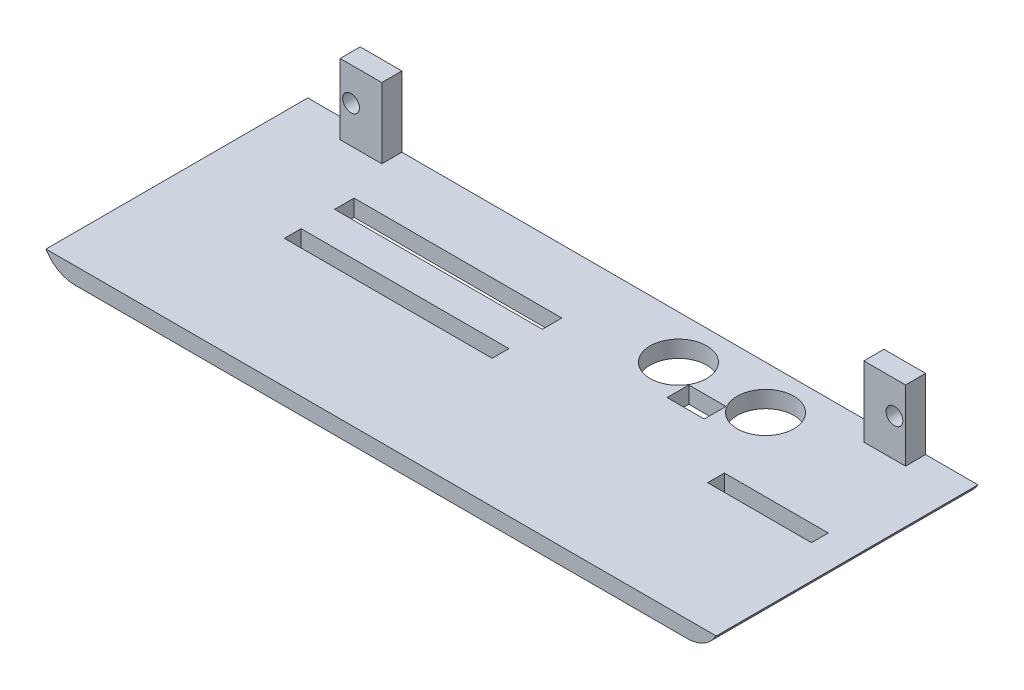
SolidWorks part; units mm, degrees
material "Aleación 1060"
ref_plane "Alzado" through (0, 0, 0) normal (0, 0, 1) x (1, 0, 0)
ref_plane "Planta" through (0, 0, 0) normal (0, 1, 0) x (1, 0, 0)
ref_plane "Vista lateral" through (0, 0, 0) normal (1, 0, 0) x (0, 0, -1)
sketch "Croquis2" plane through (0, 0, 0) normal (0, 0, 1) x (1, 0, 0)
  line L0 (64.1083, -69.3601) -> (64.1083, -63.6754) construction
  line L1 (-99.8917, -75.3601) -> (100.1083, -75.3601)
  line L2 (-99.8917, -75.3601) -> (-99.8917, 74.6399)
  line L3 (-99.8917, 74.6399) -> (100.1083, 74.6399)
  line L4 (100.1083, -75.3601) -> (100.1083, 74.6399)
  line L6 (100.1083, -69.3601) -> (-31.2492, -69.3601) construction
  line L7 (-32.0917, -69.3601) -> (-32.0917, -67.3601) construction
  line L8 (-62.0917, -69.3601) -> (-62.0917, -67.3601) construction
  line L11 (0.1083, -67.3601) -> (0.1083, -75.3601) construction
  line L15 (71.6083, -0.3601) -> (100.1083, -0.3601) construction
  line L34 (-99.8917, -0.3601) -> (-71.3917, -0.3601) construction
  line L35 (-62.0917, 70.6399) -> (64.1083, 70.6399)
  line L38 (-71.3917, -12.9024) -> (-71.3917, 12.1823)
  line L41 (-79.2417, -13.0101) -> (-71.3917, -12.9024)
  line L45 (92.1083, 45.4784) -> (92.1083, -46.1985)
  line L46 (89.1083, 45.8764) -> (89.1083, -46.5966)
  line L47 (84.1083, 12.2899) -> (84.1083, -13.0101)
  line L48 (84.1083, -13.0101) -> (79.4583, -13.0101)
  line L49 (71.6083, -13.0101) -> (71.6083, 12.2899)
  line L52 (79.4583, -13.0101) -> (71.6083, -13.0101)
  line L53 (84.1083, 12.2899) -> (79.4583, 12.2899)
  line L69 (-83.8917, -13.0101) -> (-79.2417, -13.0101)
  line L70 (-83.8917, 12.2899) -> (-83.8917, -13.0101)
  line L71 (-91.8917, 45.4784) -> (-91.8917, -46.1985)
  line L72 (-88.8917, 45.8764) -> (-88.8917, -46.5966)
  line L82 (79.4583, 12.2899) -> (71.6083, 12.2899)
  line L85 (-79.2417, 12.2899) -> (-71.3917, 12.1823)
  line L86 (-83.8917, 12.2899) -> (-79.2417, 12.2899)
  line L99 (-45.6601, 58.1834) -> (-14.3628, 58.1834)
  line L102 (64.1083, 66.6399) -> (-62.0917, 66.6399)
  line L103 (-62.0917, -71.3601) -> (64.1083, -71.3601)
  line L104 (64.1083, -67.3601) -> (-62.0917, -67.3601)
  line L118 (-45.6601, 58.1834) -> (-45.6601, 14.4146)
  line L119 (-45.6601, 14.4146) -> (-14.3628, 14.4146)
  line L120 (-14.3628, 58.1834) -> (-14.3628, 14.4146)
  line L121 (-45.6601, -4.9147) -> (-14.3628, -4.9147)
  line L122 (-45.6601, -4.9147) -> (-45.6601, -48.6834)
  line L123 (-45.6601, -48.6834) -> (-14.3628, -48.6834)
  line L124 (-14.3628, -4.9147) -> (-14.3628, -48.6834)
  line L125 (1.1959, 21.9686) -> (24.7698, 21.9686)
  line L126 (1.1959, 21.9686) -> (1.1959, -23.3553)
  line L127 (1.1959, -23.3553) -> (24.7698, -23.3553)
  line L128 (24.7698, 21.9686) -> (24.7698, -23.3553)
  circle A0 centre (89.1083, -66.5) radius 2
  arc A1 (64.1083, -71.3601) -> (64.1083, -67.3601) centre (64.1083, -69.3601) ccw
  arc A6 (-62.0917, -67.3601) -> (-62.0917, -71.3601) centre (-62.0917, -69.3601) ccw
  circle A8 centre (-88.8917, -66.5) radius 2
  arc A92 (89.1083, -46.5966) -> (92.1083, -46.1985) centre (90.6083, -46.3976) ccw
  arc A97 (-88.8917, -46.5966) -> (-91.8917, -46.1985) centre (-90.3917, -46.3976) cw
  arc A108 (-88.8917, 45.8764) -> (-91.8917, 45.4784) centre (-90.3917, 45.6774) ccw
  arc A109 (89.1083, 45.8764) -> (92.1083, 45.4784) centre (90.6083, 45.6774) cw
  circle A110 centre (89.1083, 65.7798) radius 2
  arc A113 (64.1083, 70.6399) -> (64.1083, 66.6399) centre (64.1083, 68.6399) cw
  arc A146 (-62.0917, 66.6399) -> (-62.0917, 70.6399) centre (-62.0917, 68.6399) cw
  circle A153 centre (-88.8917, 65.7798) radius 2
  circle A154 centre (-80.8654, -59.3601) radius 2.5
  circle A155 centre (81.1083, -59.3601) radius 2.5
  circle A156 centre (81.1083, 58.6399) radius 2.5
  circle A157 centre (-80.8654, 58.6399) radius 2.5
  point P0 (0, 0)
  point P78 (3.0535, -59.0858)
  point P80 (1.1959, -58.7698)
  point P84 (89.4782, -52.7527)
  point P89 (81.5012, -58.7833)
  point P95 (-80.8654, -59.3601)
  point P116 (-91.8917, -0.3601)
  point P120 (-5.0314, -61.027)
  point P121 (11.1384, -58.7698)
  point P128 (84.1083, -0.3601)
  point P135 (71.6083, -0.3601)
  point P139 (-71.3917, -0.3601)
  point P140 (-83.8917, -0.3601)
  point P143 (-88.8917, -0.3601)
  point P144 (0.0463, 58.5996)
  point P149 (89.1083, -0.3601)
  point P150 (92.1083, -0.3601)
  point P155 (81.5012, 58.0631)
  point P171 (49.6083, -0.3601)
  point P173 (46.6083, -0.3601)
  point P228 (1.1959, 58.2649)
  point P247 (7.6372, -0.3601)
  point P258 (-14.3628, -0.3601)
  point P290 (-80.8654, 58.38)
  dimension "D4" = 6
  dimension "D5" = 25
  dimension "D6" = 19.0263
  dimension "D7" = 16
  dimension "D9" = 16
  dimension "D19" = 26.8
  dimension "D32" = 8
  dimension "D22" = 3
  dimension "D8" = 19
  dimension "D1" = 200
  dimension "D2" = 150
  dimension "D10" = 11
  dimension "D11" = 11
  dimension "D35" = 12.65
  dimension "D36" = 5
  dimension "D42" = 4.65
  dimension "D43" = 12.5
extrude "Saliente-Extruir1" add sketch "Croquis2" along normal blind 2
fillet "Redondeo1" radius 10 4 edges at (-99.8917, 74.6399, 1) (-99.8917, -75.3601, 1) (100.1083, -75.3601, 1) (100.1083, 74.6399, 1)
sketch "Sketch1" plane through (0, 0, 2) normal (0, 0, 1) x (1, 0, 0)
  line L0 (-67.0718, 64.6399) -> (-67.0718, 60.6399)
  line L1 (-67.0718, 60.6399) -> (-8.8412, 60.6399)
  line L2 (-8.8412, 60.6399) -> (-8.8412, 3.6399)
  line L3 (-8.8412, 3.6399) -> (-67.0718, 3.6399)
  line L4 (-67.0718, 3.6399) -> (-67.0718, -0.3601)
  line L5 (-67.0718, -0.3601) -> (-8.8412, -0.3601)
  line L6 (-8.8412, -0.3601) -> (-8.8412, -53.3601)
  line L7 (-8.8412, -53.3601) -> (-67.0718, -53.3601)
  line L8 (-67.0718, -53.3601) -> (-67.0718, -57.5747)
  line L9 (-67.0718, -57.5747) -> (-5.0314, -57.5747)
  line L10 (-5.0314, -57.5747) -> (-5.0314, -40.9314)
  line L11 (-5.0314, -40.9314) -> (46.6083, -40.9314)
  line L12 (46.6083, -40.9314) -> (46.6083, -36.9314)
  line L13 (46.6083, -36.9314) -> (-5.0314, -36.9314)
  line L14 (-5.0314, -36.9314) -> (-5.0314, 30.0686)
  line L15 (-5.0314, 30.0686) -> (46.6083, 30.0686)
  line L16 (46.6083, 30.0686) -> (46.6083, 34.0686)
  line L17 (46.6083, 34.0686) -> (-5.0314, 34.0686)
  line L18 (-5.0314, 34.0686) -> (-5.0314, 64.6399)
  line L19 (-5.0314, 64.6399) -> (-67.0718, 64.6399)
extrude "Boss-Extrude1" add sketch "Sketch1" along normal blind 25
sketch "Sketch3" plane through (0, -57.5747, 0) normal (0, -1, 0) x (1, 0, 0)
  line L0 (-5.0314, 27) -> (-5.0314, 2) construction
  line L1 (-67.0718, 27) -> (-5.0314, 27)
  line L2 (-67.0718, 27) -> (-67.0718, 21.4692)
  line L3 (-67.0718, 21.4692) -> (-5.0314, 21.4692)
  line L4 (-5.0314, 27) -> (-5.0314, 21.4692)
extrude "Boss-Extrude2" add sketch "Sketch3" along normal blind 22
sketch "Sketch8" plane through (0, 64.6399, 0) normal (0, 1, 0) x (1, 0, 0)
  line L0 (-67.0718, -21.4692) -> (-5.0314, -21.4692)
  line L1 (-5.0314, -27) -> (-5.0314, -2) construction
  line L2 (-5.0314, -21.4692) -> (-5.0314, -27)
  line L3 (-5.0314, -27) -> (-67.0718, -27)
  line L4 (-67.0718, -27) -> (-67.0718, -21.4692)
extrude "Boss-Extrude6" add sketch "Sketch8" along normal blind 13
sketch "Sketch2" plane through (0, -75.3601, 0) normal (0, -1, 0) x (1, 0, 0)
  line L1 (-99.8917, 2) -> (100.1083, 2)
  line L2 (-99.8917, 2) -> (-99.8917, 80.1241)
  line L3 (-99.8917, 80.1241) -> (100.1083, 80.1241)
  line L4 (100.1083, 2) -> (100.1083, 80.1241)
  line L5 (-67.0718, 27) -> (-5.0314, 27)
  line L6 (-67.0718, 27) -> (-67.0718, 21.4692)
  line L7 (-67.0718, 21.4692) -> (-5.0314, 21.4692)
  line L8 (-5.0314, 27) -> (-5.0314, 21.4692)
extrude "Boss-Extrude3" add sketch "Sketch2" against normal blind 5
sketch "Sketch4" plane through (0, 64.6399, 0) normal (0, 1, 0) x (1, 0, 0)
  line L1 (-67.0718, -21.4692) -> (-5.0314, -21.4692)
  line L2 (-67.0718, -21.4692) -> (-67.0718, -27)
  line L3 (-67.0718, -27) -> (-5.0314, -27)
  line L4 (-5.0314, -21.4692) -> (-5.0314, -27)
extrude "Boss-Extrude4" add sketch "Sketch4" along normal blind 19
sketch "Sketch5" plane through (0, -75.3601, 0) normal (0, -1, 0) x (1, 0, 0)
  line L0 (0.1083, 80.1241) -> (0.1083, 0) construction
  line L1 (-84.2615, 2) -> (-76.8189, 2)
  line L2 (-84.2615, 2) -> (-84.2615, 4.9915)
  line L3 (-84.2615, 4.9915) -> (-76.8189, 4.9915)
  line L4 (-76.8189, 2) -> (-76.8189, 4.9915)
  line L5 (100.1083, 80.1241) -> (-99.8917, 80.1241) construction
  line L6 (-89.8917, 0) -> (90.1083, 0) construction
  line L7 (100.1083, 2) -> (100.1083, 80.1241) construction
  line L8 (84.478, 2) -> (84.478, 4.9915)
  line L9 (84.478, 2) -> (77.0354, 2)
  line L10 (77.0354, 2) -> (77.0354, 4.9915)
  line L11 (84.478, 4.9915) -> (77.0354, 4.9915)
  dimension "D1" = 100
extrude "Boss-Extrude5" add sketch "Sketch5" against normal blind 21
sketch "Sketch6" plane through (0, 0, 4.9915) normal (0, 0, 1) x (1, 0, 0)
  line L0 (0, 0) -> (0.1083, -75.3601) construction
  line L1 (100.1083, -75.3601) -> (-99.8917, -75.3601) construction
  circle A0 centre (-80.996, -59.2843) radius 2.5
  circle A1 centre (81.166, -59.0514) radius 2.5
extrude "Cut-Extrude1" cut sketch "Sketch6" against normal through all
fillet "Fillet1" radius 10 2 edges at (-99.8917, -75.3601, 41.0621) (100.1083, -75.3601, 41.0621)
sketch "Sketch9" plane through (0, 0, 2) normal (0, 0, 1) x (1, 0, 0)
  line L0 (-84.2615, -70.3601) -> (-84.2615, -54.3601)
  line L1 (-108.2951, 85.6815) -> (100.1083, 85.6815)
  line L2 (-108.2951, 85.6815) -> (-108.2951, -70.3601)
  line L3 (-108.2951, -70.3601) -> (-84.2615, -70.3601)
  line L4 (100.1083, 85.6815) -> (100.1083, -70.3601)
  line L5 (-84.2615, -54.3601) -> (-76.8189, -54.3601)
  line L6 (-76.8189, -54.3601) -> (-76.8189, -70.3601)
  line L7 (77.0354, -70.3601) -> (77.0354, -54.3601)
  line L8 (77.0354, -54.3601) -> (84.478, -54.3601)
  line L9 (84.478, -54.3601) -> (84.478, -70.3601)
  line L10 (-76.8189, -70.3601) -> (77.0354, -70.3601)
  line L11 (84.478, -70.3601) -> (100.1083, -70.3601)
  line L13 (-67.0718, -75.3601) -> (-5.0314, -75.3601)
  line L14 (-67.0718, -75.3601) -> (-67.0718, -79.5747)
  line L15 (-67.0718, -79.5747) -> (-5.0314, -79.5747)
  line L16 (-5.0314, -75.3601) -> (-5.0314, -79.5747)
  circle A0 centre (-80.996, -59.2843) radius 2.4639
  circle A1 centre (81.166, -59.0514) radius 2.5
extrude "Cut-Extrude2" cut sketch "Sketch9" along normal through all and the other way blind 13
sketch "Sketch10" plane through (-84.2615, 0, 0) normal (-1, 0, 0) x (0, 0, 1)
  line L1 (0, -54.3601) -> (2, -54.3601)
  line L2 (0, -54.3601) -> (0, -75.3601)
  line L3 (0, -75.3601) -> (2, -75.3601)
  line L4 (2, -54.3601) -> (2, -75.3601)
extrude "Cut-Extrude3" cut sketch "Sketch10" against normal through all and the other way blind 26
sketch "Sketch11" plane through (0, -75.3601, 0) normal (0, -1, 0) x (1, 0, 0)
  line L0 (-99.8917, 80.1241) -> (-99.8917, 2) construction
  line L1 (-67.0917, 26.7915) -> (-5.0917, 26.7915)
  line L2 (-67.0917, 26.7915) -> (-67.0917, 20.9915)
  line L3 (-67.0917, 20.9915) -> (-5.0917, 20.9915)
  line L4 (-5.0917, 26.7915) -> (-5.0917, 20.9915)
  line L5 (-84.2615, 4.9915) -> (-76.8189, 4.9915) construction
  line L7 (-67.0917, 36.7915) -> (-5.0917, 36.7915)
  line L8 (-67.0917, 36.7915) -> (-67.0917, 41.7915)
  line L9 (-67.0917, 41.7915) -> (-5.0917, 41.7915)
  line L10 (-5.0917, 36.7915) -> (-5.0917, 41.7915)
  line L11 (59.2083, 36.7915) -> (90.2083, 36.7915)
  line L12 (59.2083, 36.7915) -> (59.2083, 41.7915)
  line L13 (59.2083, 41.7915) -> (90.2083, 41.7915)
  line L14 (90.2083, 36.7915) -> (90.2083, 41.7915)
  dimension "D1" = 32.8
  dimension "D2" = 62
  dimension "D3" = 16
  dimension "D4" = 5.8
  dimension "D5" = 10
  dimension "D6" = 5
  dimension "D7" = 64.3
  dimension "D8" = 31
extrude "Cut-Extrude4" cut sketch "Sketch11" against normal through all
sketch "Croquis4" plane through (77.0354, 0, 0) normal (-1, 0, 0) x (0, 0, 1)
  line L1 (2, -54.3601) -> (4.9915, -54.3601)
  line L2 (2, -54.3601) -> (2, -70.3601)
  line L3 (2, -70.3601) -> (4.9915, -70.3601)
  line L4 (4.9915, -54.3601) -> (4.9915, -70.3601)
extrude "Saliente-Extruir2" add sketch "Croquis4" along normal blind 5
sketch "Croquis5" plane through (0, -54.3601, 0) normal (0, 1, 0) x (1, 0, 0)
  line L1 (72.0354, -2) -> (84.478, -2)
  line L2 (72.0354, -2) -> (72.0354, -4.9915)
  line L3 (72.0354, -4.9915) -> (84.478, -4.9915)
  line L4 (84.478, -2) -> (84.478, -4.9915)
extrude "Saliente-Extruir3" add sketch "Croquis5" along normal blind 5
sketch "Croquis7" plane through (0, 0, 4.9915) normal (0, 0, 1) x (1, 0, 0)
  line L1 (72.0354, -49.3601) -> (84.478, -49.3601)
  line L2 (72.0354, -49.3601) -> (72.0354, -70.3601)
  line L3 (72.0354, -70.3601) -> (84.478, -70.3601)
  line L4 (84.478, -49.3601) -> (84.478, -70.3601)
extrude "Saliente-Extruir4" add sketch "Croquis7" along normal blind 3
sketch "Croquis8" plane through (0, 0, 2) normal (0, 0, -1) x (-1, 0, 0)
  circle A0 centre (-81.166, -59.0514) radius 2.5
extrude "Cortar-Extruir3" cut sketch "Croquis8" against normal blind 15
sketch "Croquis9" plane through (-76.8189, 0, 0) normal (1, 0, 0) x (0, 0, -1)
  line L1 (-2, -70.3601) -> (-4.9915, -70.3601)
  line L2 (-2, -70.3601) -> (-2, -54.3601)
  line L3 (-2, -54.3601) -> (-4.9915, -54.3601)
  line L4 (-4.9915, -70.3601) -> (-4.9915, -54.3601)
extrude "Saliente-Extruir5" add sketch "Croquis9" along normal blind 5
sketch "Croquis10" plane through (0, -54.3601, 0) normal (0, 1, 0) x (1, 0, 0)
  line L1 (-84.2615, -2) -> (-71.8189, -2)
  line L2 (-84.2615, -2) -> (-84.2615, -4.9915)
  line L3 (-84.2615, -4.9915) -> (-71.8189, -4.9915)
  line L4 (-71.8189, -2) -> (-71.8189, -4.9915)
extrude "Saliente-Extruir6" add sketch "Croquis10" along normal blind 5
sketch "Croquis11" plane through (0, 0, 4.9915) normal (0, 0, 1) x (1, 0, 0)
  line L1 (-84.2615, -49.3601) -> (-71.8189, -49.3601)
  line L2 (-84.2615, -49.3601) -> (-84.2615, -70.3601)
  line L3 (-84.2615, -70.3601) -> (-71.8189, -70.3601)
  line L4 (-71.8189, -49.3601) -> (-71.8189, -70.3601)
extrude "Saliente-Extruir7" add sketch "Croquis11" along normal blind 3
sketch "Croquis12" plane through (0, 0, 2) normal (0, 0, -1) x (-1, 0, 0)
  circle A0 centre (80.996, -59.2843) radius 2.5
extrude "Cortar-Extruir4" cut sketch "Croquis12" against normal blind 11
sketch "Croquis13" plane through (0, -75.3601, 0) normal (0, -1, 0) x (1, 0, 0)
  line L0 (59.2083, 36.7915) -> (59.2083, 2) construction
  line L1 (14.2083, 32) -> (14.2083, 2) construction
  line L2 (51.3688, 32) -> (-99.8917, 32) construction
  line L3 (-99.8917, 80.1241) -> (-99.8917, 2) construction
  line L4 (51.3688, 32) -> (91.448, 32) construction
  line L5 (91.448, 2) -> (91.448, 80.1241) construction
  line L6 (-91.2315, 2) -> (91.448, 2) construction
  line L7 (14.2083, 5) -> (59.2083, 5) construction
  line L8 (14.2083, 25) -> (14.2083, 22.34) construction
  line L9 (14.2083, 5) -> (59.2083, 5)
  line L10 (14.2083, 5) -> (14.2083, 25)
  line L11 (14.2083, 25) -> (59.2083, 25)
  line L12 (59.2083, 5) -> (59.2083, 25)
  line L13 (-67.0917, 26.7915) -> (-67.0917, 20.9915) construction
  line L14 (14.2083, 5) -> (23.7083, 5) construction
  line L15 (14.2083, 5) -> (14.2083, 15) construction
  line L16 (31.7083, 24.34) -> (31.7083, 19.34)
  line L17 (14.2083, 15) -> (23.7083, 15) construction
  line L18 (31.7083, 24.34) -> (41.7083, 24.34)
  line L19 (41.7083, 24.34) -> (41.7083, 19.34)
  line L20 (41.7083, 19.34) -> (31.7083, 19.34)
  line L21 (23.7083, 15) -> (23.7083, 5) construction
  line L22 (23.7083, 15) -> (49.7083, 15) construction
  line L23 (-67.0917, 20.9915) -> (-5.0917, 20.9915) construction
  circle A0 centre (23.7083, 15) radius 8.45
  circle A1 centre (49.7083, 15) radius 8.45
  dimension "D2" = 3
  dimension "D9" = 26
sketch "Croquis15" plane through (0, -75.3601, 0) normal (0, -1, 0) x (1, 0, 0)
  line L0 (31.7083, 24.34) -> (31.7083, 19.34)
  line L1 (31.7083, 19.34) -> (41.7083, 19.34)
  line L2 (41.7083, 19.34) -> (41.7083, 24.34)
  line L3 (41.7083, 24.34) -> (31.7083, 24.34)
  circle A0 centre (23.7083, 15) radius 8.45
  circle A1 centre (49.7083, 15) radius 8.45
extrude "Cortar-Extruir8" cut sketch "Croquis15" against normal blind 111
sketch "Croquis16" plane through (0, -75.3601, 0) normal (0, -1, 0) x (1, 0, 0)
  line L2 (31.7083, 25.84) -> (41.7083, 25.84)
  line L4 (31.7083, 24.34) -> (41.7083, 24.34)
  line L5 (31.7083, 19.34) -> (31.1683, 19.34)
  line L6 (31.1683, 19.34) -> (31.1683, 25.84)
  line L7 (31.1683, 25.84) -> (31.7083, 25.84)
  line L10 (41.7083, 19.34) -> (42.2483, 19.34)
  line L11 (42.2483, 19.34) -> (42.2483, 25.84)
  line L12 (42.2483, 25.84) -> (41.7083, 25.84)
  line L13 (31.7083, 19.34) -> (31.7083, 24.34)
  line L14 (41.7083, 24.34) -> (41.7083, 19.34) construction
  line L15 (41.7083, 24.34) -> (41.7083, 19.34)
  dimension "D1" = 0.54
  dimension "D2" = 0.54
extrude "Cortar-Extruir10" cut sketch "Croquis16" against normal blind 10
